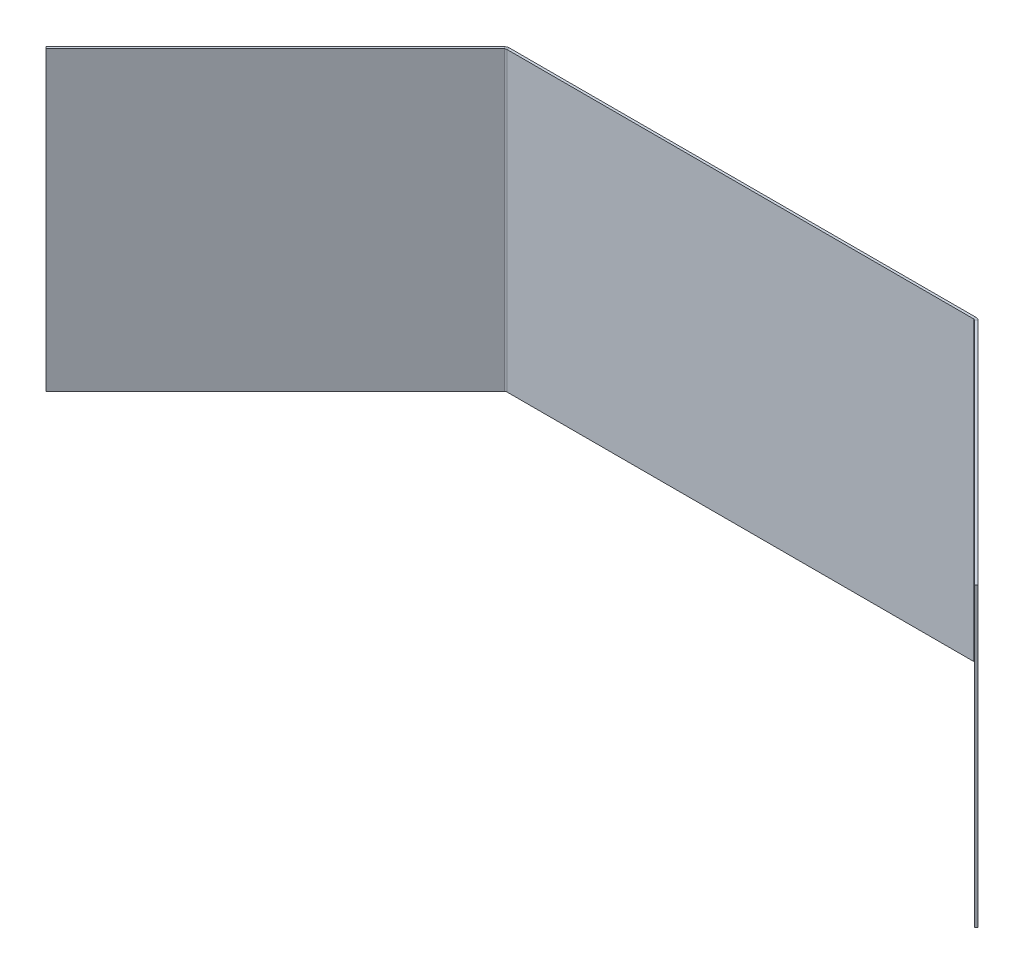
SolidWorks part; units mm, degrees
note: The reader was unsure of these and kept them because the rebuilt part matched: bend radius of "基体折弯1", "基体折弯2".
material "镀铬不锈钢"
ref_plane "前视基准面" through (0, 0, 0) normal (0, 0, 1) x (1, 0, 0)
ref_plane "上视基准面" through (0, 0, 0) normal (0, 1, 0) x (1, 0, 0)
ref_plane "右视基准面" through (0, 0, 0) normal (1, 0, 0) x (0, 0, -1)
sketch "草图1" plane through (0, 0, 0) normal (0, 1, 0) x (1, 0, 0)
  line L2 (-185.625, 0) -> (185.625, 0)
  line L3 (-185.625, 0) -> (-367.6979, -182.0729)
  line L4 (0, 0) -> (0, -217.7614) construction
  line L5 (185.625, 0) -> (367.6979, -182.0729)
  dimension "D1" = 371.25
  dimension "D2" = 45
  dimension "D3" = 257.49
base flange "基体-法兰1" sketch "草图1" end condition mid plane depth 235 reverse direction no thickness 2 reverse thickness direction yes bend radius 2
bend "基体折弯1" bend radius 2 bend angle 45 parameters "D5"=1
bend "基体折弯2" bend radius 2 bend angle 45 parameters "D5"=2
sketch "折弯-线1" [suppressed] plane through (0, 0, 0) normal (0, 1, 0) x (1, 0, 0)
sketch "边界框1" [suppressed] plane through (0, 0, 0) normal (0, 1, 0) x (1, 0, 0)
sheet metal parameters "钣金6" thickness 2 parameters "D1"=2
flat pattern "平板型式6" [suppressed]
sketch "折弯-线2" plane through (0, 0, -2) normal (0, 0, -1) x (-1, 0, 0)
  line L2 (185.9747, 117.5) -> (185.9747, -117.5) construction
  line L3 (-185.9747, -117.5) -> (-185.9747, 117.5) construction
  line L4 (185.9747, 117.5) -> (185.9747, -117.5) construction
  line L5 (-185.9747, -117.5) -> (-185.9747, 117.5) construction
sketch3d "边界框2" [suppressed]
  line L0 (258.1893, -235, 0) -> (-629.4393, -235, 0) construction
  line L1 (258.1893, 0, 0) -> (-629.4393, 0, 0) construction
  line L2 (258.1893, -235, 0) -> (258.1893, 0, 0) construction
  line L3 (-629.4393, -235, 0) -> (-629.4393, 0, 0) construction
bend of the flat pattern "展开-<基体折弯1>1"
bend of the flat pattern "展开-<基体折弯2>1"
